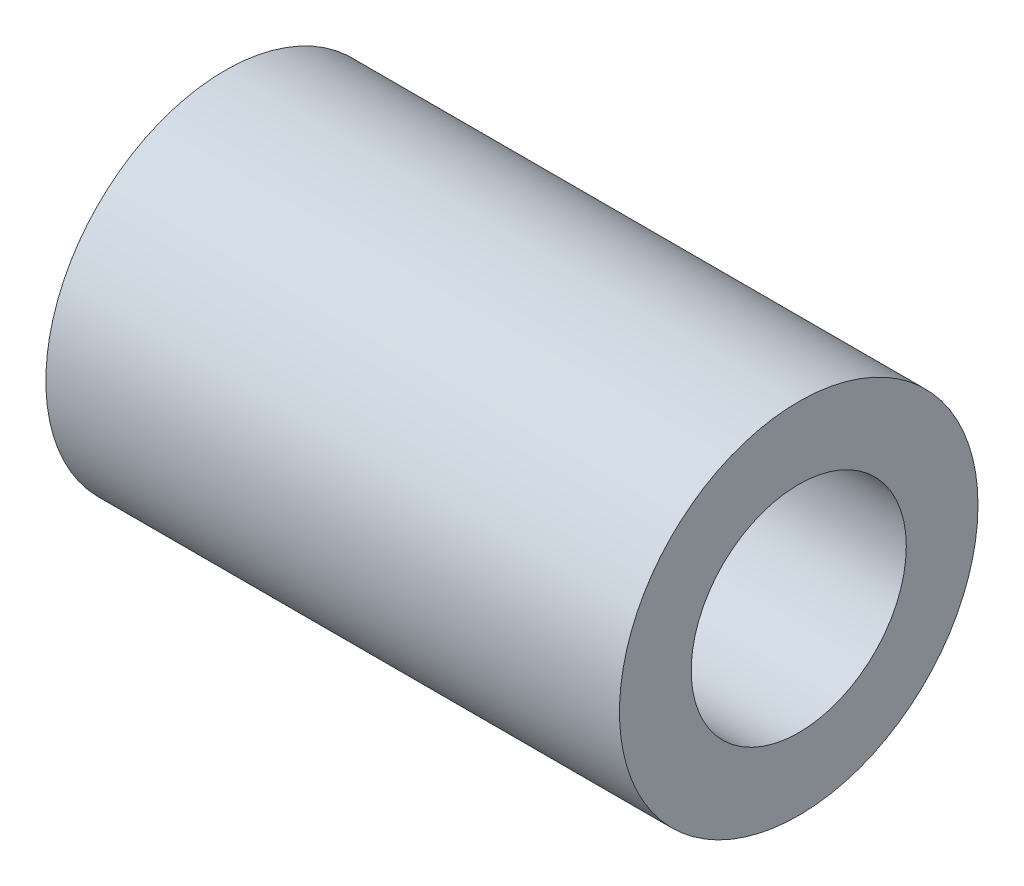
SolidWorks part; units mm, degrees
material "Thornel Mat VMA"
ref_plane "Front Plane" through (0, 0, 0) normal (0, 0, 1) x (1, 0, 0)
ref_plane "Top Plane" through (0, 0, 0) normal (0, 1, 0) x (1, 0, 0)
ref_plane "Right Plane" through (0, 0, 0) normal (1, 0, 0) x (0, 0, -1)
sketch "Sketch1" plane through (0, 0, 0) normal (1, 0, 0) x (0, 0, -1)
  circle A0 centre (0, 0) radius 4.7625
  circle A1 centre (0, 0) radius 7.9375
  dimension "D1" = 9.525
  dimension "D2" = 15.875
extrude "Boss-Extrude1" add sketch "Sketch1" along normal mid plane 25.4
